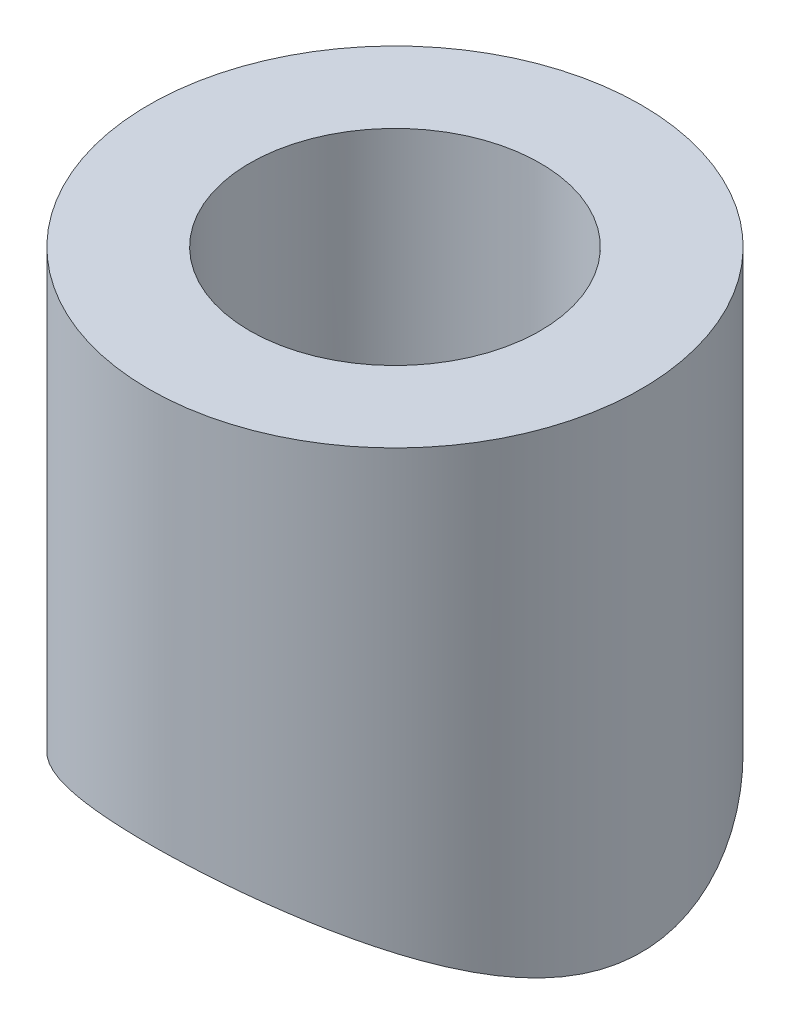
SolidWorks part; units mm, degrees
material "6063-T6"
ref_plane "Front Plane" through (0, 0, 0) normal (0, 0, 1) x (1, 0, 0)
ref_plane "Top Plane" through (0, 0, 0) normal (0, 1, 0) x (1, 0, 0)
ref_plane "Right Plane" through (0, 0, 0) normal (1, 0, 0) x (0, 0, -1)
sketch "Sketch1" plane through (0, 0, 0) normal (0, 1, 0) x (1, 0, 0)
  circle A0 centre (0, 0) radius 10
  point P4 (0, 0)
  dimension "D1" = 20
extrude "Boss-Extrude1" add sketch "Sketch1" along normal blind 20
sketch "Sketch2" plane through (0, 0, 0) normal (0, 0, 1) x (1, 0, 0)
  circle A0 centre (0, -11) radius 15
  dimension "D1" = 30
  dimension "D2" = 11
extrude "Cut-Extrude1" cut sketch "Sketch2" along normal through all both and the other way through all
hole_wizard "G1/4 Tapped Hole1" positions "Sketch3" profile "Sketch4" tap size "G1/4" standard "ISO" end condition through all
sketch "Sketch3" plane through (0, 20, 0) normal (0, 1, 0) x (1, 0, 0)
  point P0 (0, 0)
sketch "Sketch4" plane through (0, 20, 0) normal (1, 0, 0) x (0, 0, 1)
  line L0 (0, 0) -> (0, 20.58)
  line L1 (0, 20.58) -> (5.9, 20.58)
  line L2 (5.9, 20.58) -> (5.9, 0)
  line L5 (5.9, 0) -> (0, 0)
  line L11 (0, -6.35) -> (0, 107.95) construction
  dimension "Thru Tap Drill Dia." = 11.8
  dimension "Thru Tap Drill Depth" = 20.58
cosmetic thread "Hole Thread1"
